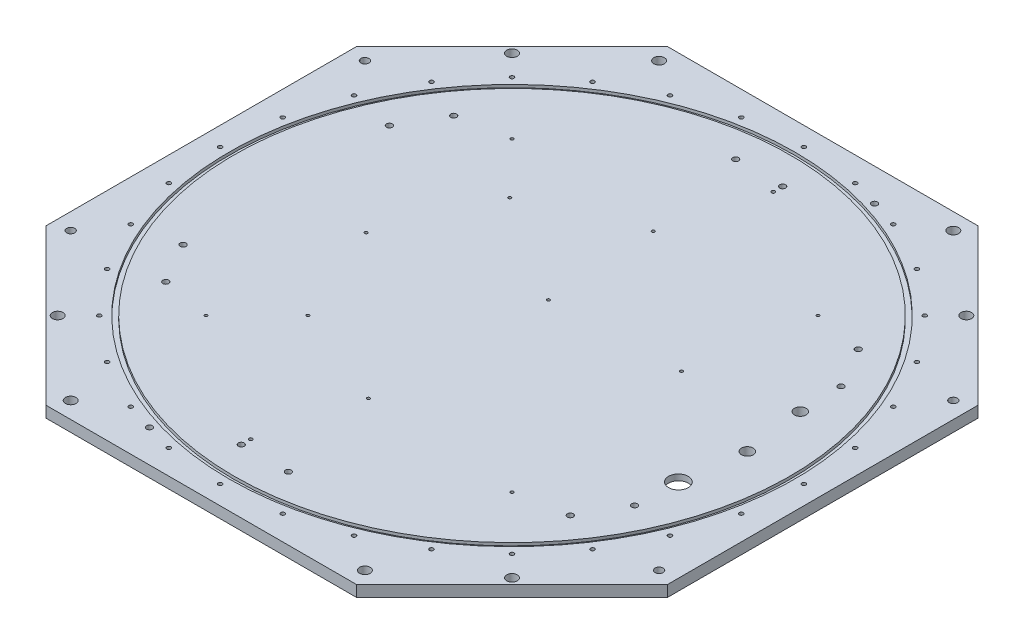
SolidWorks part; units mm, degrees
material "AISI 304"
ref_plane "Front" through (0, 0, 0) normal (0, 0, 1) x (1, 0, 0)
ref_plane "Top" through (0, 0, 0) normal (0, 1, 0) x (1, 0, 0)
ref_plane "Right" through (0, 0, 0) normal (1, 0, 0) x (0, 0, -1)
ref_axis "Axis1" through (0, -5.2388, 0) along (0, 1, 0)
sketch "Sketch1" plane through (0, 0, 0) normal (0, 1, 0) x (1, 0, 0)
  line L0 (-131.9798, 264) -> (131.9798, 264)
  line L1 (131.9798, 264) -> (264, 131.9798)
  line L2 (264, 131.9798) -> (264, -131.9798)
  line L3 (264, 0) -> (0, 0) construction
  line L4 (0, 0) -> (0, 264) construction
  line L5 (131.9798, -264) -> (264, -131.9798)
  line L6 (-131.9798, -264) -> (131.9798, -264)
  line L7 (-131.9798, -264) -> (-264, -131.9798)
  line L8 (-264, 131.9798) -> (-264, -131.9798)
  line L9 (-131.9798, 264) -> (-264, 131.9798)
  point P12 (0, -264)
  point P21 (0, 0)
  dimension "D1" = 528
  dimension "D2" = 280
extrude "Base Plate Profile" add sketch "Sketch1" along normal mid plane 9.525
hole_wizard "M3 Clearance Hole - For Cylinder" positions "Sketch2" profile "Sketch3" hole size "M3" standard "ANSI Metric" end condition up to next
sketch "Sketch2" plane through (0, 4.7625, 0) normal (0, 1, 0) x (1, 0, 0)
  line L0 (-248, 0) -> (248, 0) construction
  point P0 (248, 0)
  point P6 (243.2347, -48.3824)
  point P7 (229.1221, -94.9055)
  point P8 (206.2045, -137.7814)
  point P9 (175.3625, -175.3625)
  point P10 (137.7814, -206.2045)
  point P11 (94.9055, -229.1221)
  point P12 (48.3824, -243.2347)
  point P13 (0, -248)
  point P14 (-48.3824, -243.2347)
  point P15 (-94.9055, -229.1221)
  point P16 (-137.7814, -206.2045)
  point P17 (-175.3625, -175.3625)
  point P18 (-206.2045, -137.7814)
  point P19 (-229.1221, -94.9055)
  point P20 (-243.2347, -48.3824)
  point P21 (-248, 0)
  point P22 (-243.2347, 48.3824)
  point P23 (-229.1221, 94.9055)
  point P24 (-206.2045, 137.7814)
  point P25 (-175.3625, 175.3625)
  point P26 (-137.7814, 206.2045)
  point P27 (-94.9055, 229.1221)
  point P28 (-48.3824, 243.2347)
  point P29 (0, 248)
  point P30 (48.3824, 243.2347)
  point P31 (94.9055, 229.1221)
  point P32 (137.7814, 206.2045)
  point P33 (175.3625, 175.3625)
  point P34 (206.2045, 137.7814)
  point P35 (229.1221, 94.9055)
  point P36 (243.2347, 48.3824)
  dimension "D2" = 496
  dimension "D1" = 32
sketch "Sketch3" plane through (248, 4.7625, 0) normal (1, 0, 0) x (0, 0, 1)
  line L0 (0, 0) -> (0, 9.525)
  line L1 (0, 9.525) -> (1.7, 9.525)
  line L2 (1.7, 9.525) -> (1.7, 0)
  line L5 (1.7, 0) -> (0, 0)
  line L11 (0, -6.35) -> (0, 107.95) construction
  dimension "Thru Hole Dia." = 3.4
  dimension "Thru Hole Depth" = 9.525
hole_wizard "M6x1 Tapped Hole - For Support Pillars" positions "Sketch10" profile "Sketch11" tap size "M6x1.0" standard "ANSI Metric"
sketch "Sketch10" plane through (0, 4.7625, 0) normal (0, 1, 0) x (1, 0, 0)
  line L0 (-20, 210) -> (0, 210) construction
  line L1 (0, 210) -> (20, 210) construction
  line L6 (0, 0) -> (0, 210) construction
  line L7 (-20, -210) -> (20, -210) construction
  line L9 (0, -210) -> (0, 0) construction
  point P0 (-20, 210)
  point P2 (20, 210)
  point P39 (171.8653, 122.3205)
  point P40 (191.8653, 87.6795)
  point P41 (191.8653, -87.6795)
  point P42 (171.8653, -122.3205)
  point P43 (20, -210)
  point P44 (-20, -210)
  point P45 (-171.8653, -122.3205)
  point P46 (-191.8653, -87.6795)
  point P47 (-191.8653, 87.6795)
  point P48 (-171.8653, 122.3205)
  dimension "D1" = 40
  dimension "D2" = 6
  dimension "D3" = 210
cosmetic thread "Hole Thread1" parameters "D1"=6, "D2"=6
cosmetic thread "Hole Thread2" parameters "D1"=6, "D2"=6
cosmetic thread "Hole Thread3" parameters "D1"=6, "D2"=6
cosmetic thread "Hole Thread4" parameters "D1"=6, "D2"=6
cosmetic thread "Hole Thread5" parameters "D1"=6, "D2"=6
cosmetic thread "Hole Thread6" parameters "D1"=6, "D2"=6
cosmetic thread "Hole Thread7" parameters "D1"=6, "D2"=6
cosmetic thread "Hole Thread8" parameters "D1"=6, "D2"=6
cosmetic thread "Hole Thread9" parameters "D1"=6, "D2"=6
cosmetic thread "Hole Thread10" parameters "D1"=6, "D2"=6
cosmetic thread "Hole Thread11" parameters "D1"=6, "D2"=6
cosmetic thread "Hole Thread12" parameters "D1"=6, "D2"=6
sketch "Sketch11" plane through (-20, 4.7625, -210) normal (1, 0, 0) x (0, 0, 1)
  line L0 (0, 0) -> (0, 7.5022)
  line L1 (0, 7.5022) -> (2.5, 6)
  line L2 (2.5, 6) -> (2.5, 0)
  line L5 (2.5, 0) -> (0, 0)
  line L10 (0, 7.5022) -> (-2.5, 6) construction
  line L11 (0, -6.35) -> (0, 107.95) construction
  dimension "Tap Drill Dia." = 5
  dimension "Tap Drill Depth" = 6
  dimension "Drill Angle" = 118
hole_wizard "Ø3.0mm Dowel Hole - For Support Pillars" positions "Sketch12" profile "Sketch13" hole size "Ø3.0" standard "ANSI Metric"
sketch "Sketch12" plane through (0, 4.7625, 0) normal (0, 1, 0) x (1, 0, 0)
  line L1 (20, 202) -> (20, 210) construction
  line L3 (-20, -210) -> (-20, -202) construction
  point P0 (20, 202)
  point P2 (-20, -202)
  dimension "D1" = 8
sketch "Sketch13" plane through (20, 4.7625, -202) normal (1, 0, 0) x (0, 0, 1)
  line L0 (0, 0) -> (0, 6.9013)
  line L1 (0, 6.9013) -> (1.5, 6)
  line L2 (1.5, 6) -> (1.5, 0)
  line L5 (1.5, 0) -> (0, 0)
  line L10 (0, 6.9013) -> (-1.5, 6) construction
  line L11 (0, -6.35) -> (0, 107.95) construction
  dimension "Hole Dia." = 3
  dimension "Hole Depth" = 6
  dimension "Drill Angle" = 118
hole_wizard "M3x0.5 Tapped Hole - For PCB Standoffs" positions "Sketch14" profile "Sketch15" tap size "M3x0.5" standard "ANSI Metric"
sketch "Sketch14" plane through (0, 4.7625, 0) normal (0, 1, 0) x (1, 0, 0)
  line L13 (-150, -150) -> (150, -150) construction
  line L14 (-150, -150) -> (-150, 150) construction
  line L15 (-150, 150) -> (150, 150) construction
  line L16 (150, -150) -> (150, 150) construction
  line L17 (-150, -150) -> (150, 150) construction
  line L18 (-150, 150) -> (150, -150) construction
  point P133 (-130, -130)
  point P136 (130, -130)
  point P138 (130, 130)
  point P140 (-130, 130)
  point P143 (-86.8, -86.7)
  point P145 (0, -122)
  point P149 (-123, -1)
  point P152 (-87.7, 85.8)
  point P154 (4, 27)
  point P157 (-2, 122)
  point P159 (113, 31)
  dimension "D1" = 300
  dimension "D3" = 63.2
  dimension "D4" = 63.3
  dimension "D5" = 28
  dimension "D2" = 20
  dimension "D6" = 27
  dimension "D7" = 149
  dimension "D8" = 235.8
  dimension "D9" = 62.3
  dimension "D10" = 154
  dimension "D11" = 177
  dimension "D12" = 148
  dimension "D13" = 272
  dimension "D14" = 181
  dimension "D15" = 263
sketch "Sketch15" plane through (113, 4.7625, -31) normal (1, 0, 0) x (0, 0, 1)
  line L0 (0, 0) -> (0, 7.2511)
  line L1 (0, 7.2511) -> (1.25, 6.5)
  line L2 (1.25, 6.5) -> (1.25, 0)
  line L5 (1.25, 0) -> (0, 0)
  line L10 (0, 7.2511) -> (-1.25, 6.5) construction
  line L11 (0, -6.35) -> (0, 107.95) construction
  dimension "Tap Drill Dia." = 2.5
  dimension "Tap Drill Depth" = 6.5
  dimension "Drill Angle" = 118
cosmetic thread "Hole Thread13" parameters "D1"=5, "D2"=3
cosmetic thread "Hole Thread14" parameters "D1"=5, "D2"=3
cosmetic thread "Hole Thread15" parameters "D1"=5, "D2"=3
cosmetic thread "Hole Thread16" parameters "D1"=5, "D2"=3
cosmetic thread "Hole Thread17" parameters "D1"=5, "D2"=3
cosmetic thread "Hole Thread18" parameters "D1"=5, "D2"=3
cosmetic thread "Hole Thread19" parameters "D1"=5, "D2"=3
cosmetic thread "Hole Thread20" parameters "D1"=5, "D2"=3
cosmetic thread "Hole Thread21" parameters "D1"=5, "D2"=3
cosmetic thread "Hole Thread22" parameters "D1"=5, "D2"=3
cosmetic thread "Hole Thread23" parameters "D1"=5, "D2"=3
sketch "PCB Size Outline" plane through (0, -4.7625, 0) normal (0, -1, 0) x (1, 0, 0)
  line L1 (-150, -150) -> (150, -150)
  line L2 (-150, -150) -> (-150, 150)
  line L3 (-150, 150) -> (150, 150)
  line L4 (150, -150) -> (150, 150)
  line L5 (-150, -150) -> (150, 150) construction
  line L6 (-150, 150) -> (150, -150) construction
  point P0 (0, 0)
  dimension "D1" = 300
hole_wizard "M8 Clearance Hole - For Lifting / Alignment" positions "Sketch16" profile "Sketch17" hole size "M8" standard "ANSI Metric" end condition up to next
sketch "Sketch16" plane through (0, 4.7625, 0) normal (0, 1, 0) x (1, 0, 0)
  line L0 (-193.0402, 193.0402) -> (-193.0402, -193.0402) construction
  line L1 (-193.0402, -193.0402) -> (193.0402, -193.0402) construction
  line L2 (193.0402, -193.0402) -> (193.0402, 193.0402) construction
  line L3 (193.0402, 193.0402) -> (-193.0402, 193.0402) construction
  line L5 (-193.0402, 193.0402) -> (193.0402, -193.0402) construction
  point P0 (-193.0402, -193.0402)
  point P6 (-193.0402, 193.0402)
  point P7 (193.0402, 193.0402)
  point P8 (193.0402, -193.0402)
  dimension "D2" = 546
  dimension "D1" = 4
sketch "Sketch17" plane through (-193.0402, 4.7625, 193.0402) normal (1, 0, 0) x (0, 0, 1)
  line L0 (0, 0) -> (0, 9.525)
  line L1 (0, 9.525) -> (4.5, 9.525)
  line L2 (4.5, 9.525) -> (4.5, 0)
  line L5 (4.5, 0) -> (0, 0)
  line L11 (0, -6.35) -> (0, 107.95) construction
  dimension "Thru Hole Dia." = 9
  dimension "Thru Hole Depth" = 9.525
hole_wizard "M8x1.25 Tapped Hole -For Super Structure" positions "Sketch18" profile "Sketch19" tap size "M8x1.25" standard "ANSI Metric" end condition up to next
sketch "Sketch18" plane through (0, 4.7625, 0) normal (0, 1, 0) x (1, 0, 0)
  line L0 (-264, 0) -> (0, 0) construction
  line L1 (-264, 131.9798) -> (-264, -131.9798) construction
  line L2 (0, 0) -> (0, -264) construction
  line L3 (-131.9798, -264) -> (131.9798, -264) construction
  line L5 (0, 0) -> (-197.9899, -197.9899) construction
  line L6 (-264, -131.9798) -> (-131.9798, -264) construction
  point P22 (-250, -125)
  point P25 (-250, 125)
  point P27 (250, -125)
  point P28 (250, 125)
  dimension "D2" = 250
  dimension "D3" = 500
sketch "Sketch19" plane through (250, 4.7625, -125) normal (1, 0, 0) x (0, 0, 1)
  line L0 (0, 0) -> (0, 9.525)
  line L1 (0, 9.525) -> (3.4, 9.525)
  line L2 (3.4, 9.525) -> (3.4, 0)
  line L5 (3.4, 0) -> (0, 0)
  line L11 (0, -6.35) -> (0, 107.95) construction
  dimension "Thru Tap Drill Dia." = 6.8
  dimension "Thru Tap Drill Depth" = 9.525
cosmetic thread "Hole Thread34" parameters "D2"=8
cosmetic thread "Hole Thread35" parameters "D2"=8
cosmetic thread "Hole Thread37" parameters "D2"=8
cosmetic thread "Hole Thread39" parameters "D2"=8
hole_wizard "7/16-20 Tapped Hole - For Penetrator" positions "Sketch25" profile "Sketch26" tap size "7/16-20" standard "ANSI Inch" end condition up to next
sketch "Sketch25" plane through (0, -4.7625, 0) normal (0, -1, 0) x (-1, 0, 0)
  point P0 (-200, 0)
  dimension "D1" = 200
cosmetic thread "Hole Thread32" parameters "D2"=11.1125
sketch "Sketch26" plane through (200, -4.7625, 0) normal (1, 0, 0) x (0, 0, -1)
  line L0 (0, 0) -> (0, 9.525)
  line L1 (0, 9.525) -> (4.9606, 9.525)
  line L2 (4.9606, 9.525) -> (4.9606, 0)
  line L5 (4.9606, 0) -> (0, 0)
  line L11 (0, -6.35) -> (0, 107.95) construction
  dimension "Thru Tap Drill Dia." = 9.9212
  dimension "Thru Tap Drill Depth" = 9.525
sketch "Sketch28" plane through (0, 4.7625, 0) normal (0, 1, 0) x (1, 0, 0)
  line L0 (-150, -150) -> (150, 150) construction
  circle A0 centre (0, 0) radius 240.5
  circle A1 centre (0, 0) radius 236.3344
  dimension "D1" = 481
  dimension "D2" = 4.1656
extrude "O-ring Groove" cut sketch "Sketch28" against normal blind 2.413
sketch "Sketch_thickness" [suppressed] plane through (0, 0, 0) normal (1, 0, 0) x (0, 0, -1)
  line L0 (-88.2215, 4.7625) -> (-88.2215, -0.2425)
  line L1 (-131.9798, 4.7625) -> (131.9798, 4.7625) construction
  line L2 (-88.2215, -0.2425) -> (-88.2215, -4.7625)
  line L3 (-150, -4.7625) -> (150, -4.7625) construction
  dimension "D1" = 5.005
  dimension "D2" = 4.52
pattern_circular "CirPattern_extraCables" count 2 every 15 about axis through (0, -5.2388, 0) along (0, 1, 0) of "7/16-20 Tapped Hole - For Penetrator"
hole_wizard "5/8 Clearance Hole1" positions "Sketch32" profile "Sketch33" hole size "5/8" standard "ANSI Inch" end condition up to next
sketch "Sketch32" plane through (0, 4.7625, 0) normal (0, 1, 0) x (1, 0, 0)
  line L0 (0, 0) -> (193.1852, -51.7638) construction
  line L2 (0, 0) -> (200, 0) construction
  point P0 (193.1852, -51.7638)
  dimension "D1" = 200
  dimension "D2" = 15
sketch "Sketch33" plane through (193.1852, 4.7625, 51.7638) normal (1, 0, 0) x (0, 0, 1)
  line L0 (0, 0) -> (0, 9.525)
  line L1 (0, 9.525) -> (8.3337, 9.525)
  line L2 (8.3337, 9.525) -> (8.3337, 0)
  line L5 (8.3337, 0) -> (0, 0)
  line L11 (0, -6.35) -> (0, 107.95) construction
  dimension "Thru Hole Dia." = 16.6675
  dimension "Thru Hole Depth" = 9.525
sketch "Sketch35" plane through (0, -4.7625, 0) normal (0, -1, 0) x (1, 0, 0)
  circle A0 centre (193.1852, 51.7638) radius 18
  dimension "D1" = 36
extrude "Cut-Extrude1" cut sketch "Sketch35" against normal blind 4.5
hole_wizard "M8 Clearance Hole" positions "Sketch37" profile "Sketch39" hole size "M8" standard "ANSI Metric" end condition up to next
sketch "Sketch37" plane through (-28.1239, 4.7625, -48.0675) normal (0, 1, 0) x (1, 0, 0)
  line L0 (-235.8761, -48.0675) -> (28.1239, -48.0675) construction
  line L2 (28.1239, -48.0675) -> (28.1239, -312.0675) construction
  line L5 (28.1239, -48.0675) -> (-169.866, -246.0574) construction
  line L7 (-103.8559, -312.0675) -> (160.1037, -312.0675) construction
  line L8 (-235.8761, 83.9123) -> (-235.8761, -180.0473) construction
  line L9 (-235.8761, -180.0473) -> (-103.8559, -312.0675) construction
  point P0 (-96.8761, -298.0675)
  point P24 (-96.8761, 201.9325)
  point P26 (153.1239, -298.0675)
  point P29 (153.1239, 201.9325)
  dimension "D1" = 250
  dimension "D2" = 500
sketch "Sketch39" plane through (-125, 4.7625, 250) normal (1, 0, 0) x (0, 0, 1)
  line L0 (0, 0) -> (0, 9.525)
  line L1 (0, 9.525) -> (4.5, 9.525)
  line L2 (4.5, 9.525) -> (4.5, 0)
  line L5 (4.5, 0) -> (0, 0)
  line L11 (0, -6.35) -> (0, 107.95) construction
  dimension "Thru Hole Dia." = 9
  dimension "Thru Hole Depth" = 9.525
hole_wizard "Ø5.0mm Dowel Hole1" positions "Sketch42" profile "Sketch43" hole size "Ø5.0" standard "ANSI Metric"
sketch "Sketch42" plane through (0, 4.7625, 0) normal (0, 1, 0) x (1, 0, 0)
  point P0 (71.7003, 236.3643)
  point P3 (-71.7003, -236.3643)
sketch "Sketch43" plane through (71.7003, 4.7625, -236.3643) normal (1, 0, 0) x (0, 0, 1)
  line L0 (0, 0) -> (0, 6.5172)
  line L1 (0, 6.5172) -> (2.525, 5)
  line L2 (2.525, 5) -> (2.525, 0)
  line L5 (2.525, 0) -> (0, 0)
  line L10 (0, 6.5172) -> (-2.525, 5) construction
  line L11 (0, -6.35) -> (0, 107.95) construction
  dimension "Hole Dia." = 5.05
  dimension "Hole Depth" = 5
  dimension "Drill Angle" = 118
sketch "Sketch44" plane through (0, 0, 0) normal (0, 0, 1) x (1, 0, 0)
  line L0 (0, 0) -> (0, 113.0488) construction
